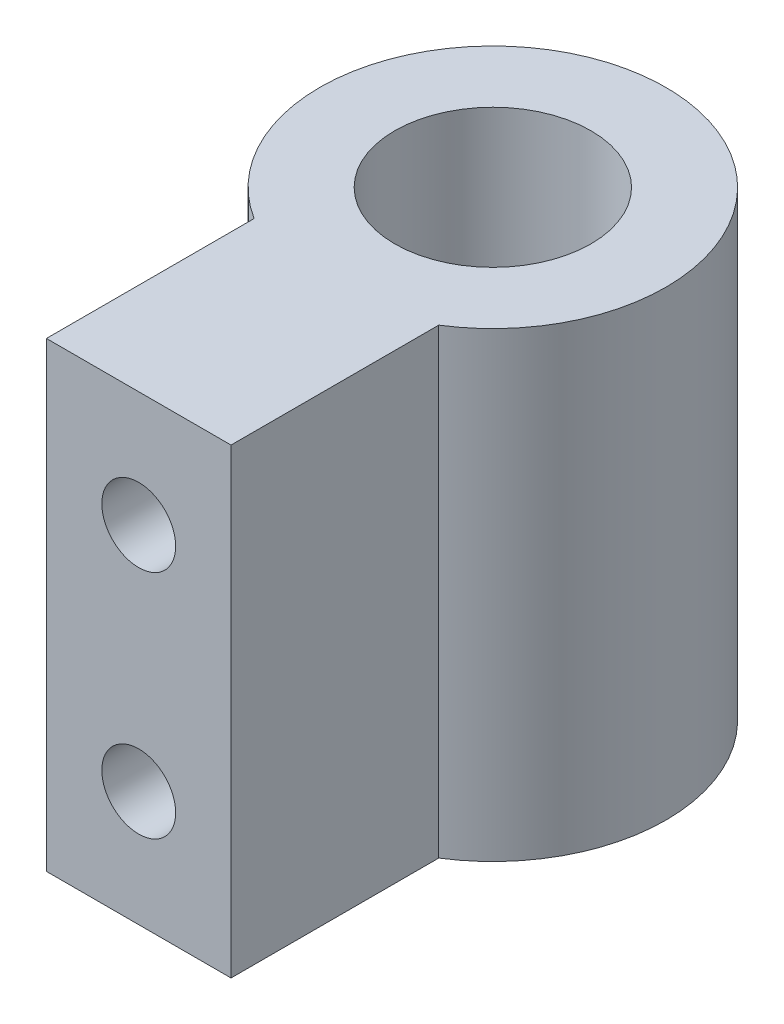
SolidWorks part; units mm, degrees
ref_plane "Front Plane" through (0, 0, 0) normal (0, 0, 1) x (1, 0, 0)
ref_plane "Top Plane" through (0, 0, 0) normal (0, 1, 0) x (1, 0, 0)
ref_plane "Right Plane" through (0, 0, 0) normal (1, 0, 0) x (0, 0, -1)
sketch "Sketch1" plane through (0, 0, 0) normal (0, 1, 0) x (1, 0, 0)
  line L9 (-5.08, -14.4072) -> (5.08, -14.4072)
  line L10 (-5.08, -14.4072) -> (-5.08, -19.4872)
  line L11 (-5.08, -19.4872) -> (5.08, -19.4872)
  line L12 (5.08, -14.4072) -> (5.08, -19.4872)
  line L13 (-5.08, -8.0572) -> (5.08, -8.0572)
  line L14 (-5.08, -8.0572) -> (-5.08, -14.4072)
  line L15 (-5.08, -14.4072) -> (5.08, -14.4072)
  line L16 (5.08, -8.0572) -> (5.08, -14.4072)
  circle A2 centre (0, 0) radius 9.525
  circle A3 centre (0, 0) radius 5.3975
  point P3 (0, -9.525)
  dimension "D1" = 10.795
  dimension "D2" = 19.05
  dimension "D3" = 10.16
  dimension "D4" = 6.35
  dimension "D5" = 5.08
extrude "Boss-Extrude1" add sketch "Sketch1" along normal blind 25.4 contours L12 L9 L10 L11 | A2 | A3 A2 | L10 L9 L12 L11 | A2 | A3 region at (0, 0, 11.7121) region at (0, 0, 16.9472) region at (-4.4758, 0, -8.1131)
sketch "Sketch4" plane through (0, 0, 19.4872) normal (0, 0, 1) x (1, 0, 0)
  line L0 (-5.08, 25.4) -> (5.08, 25.4) construction
  circle A0 centre (0, 19.05) radius 2.032
  circle A1 centre (0, 6.35) radius 2.032
  point P7 (0, 25.4)
  dimension "D1" = 4.064
  dimension "D2" = 12.7
  dimension "D3" = 6.35
extrude "Cut-Extrude2" cut sketch "Sketch4" against normal blind 12.7
